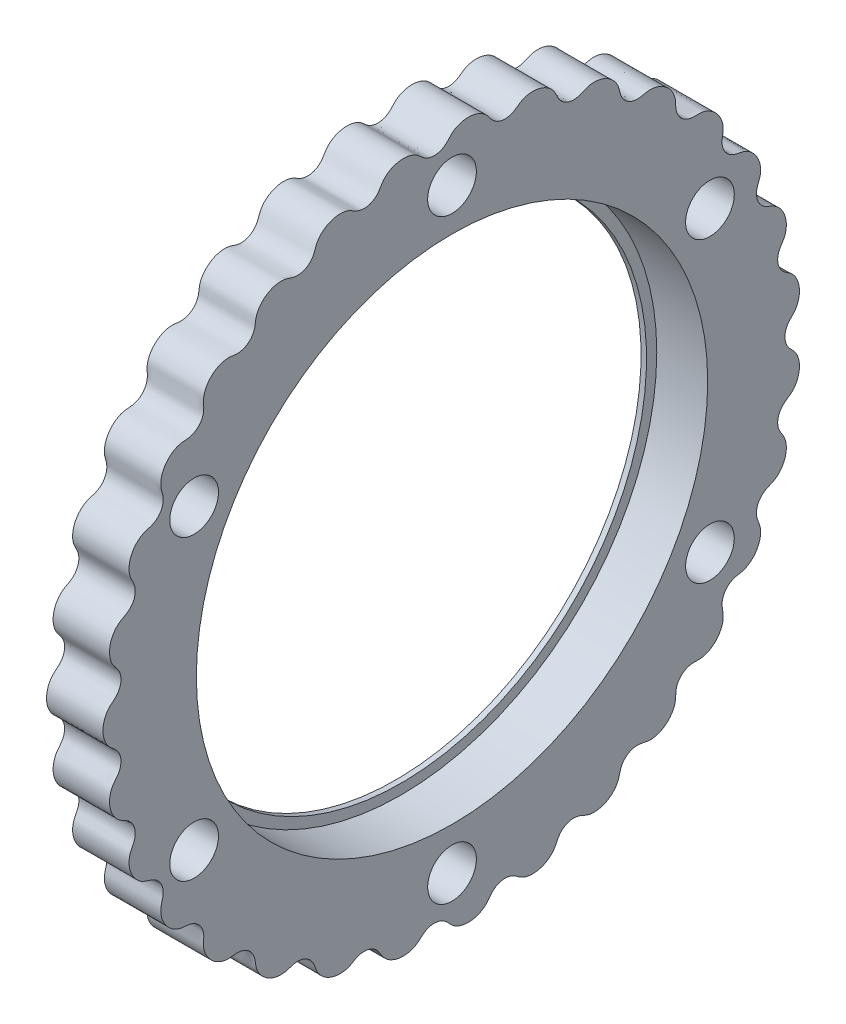
SolidWorks part; units mm, degrees
ref_plane "Front Plane" through (0, 0, 0) normal (0, 0, 1) x (1, 0, 0)
ref_plane "Top Plane" through (0, 0, 0) normal (0, 1, 0) x (1, 0, 0)
ref_plane "Right Plane" through (0, 0, 0) normal (1, 0, 0) x (0, 0, -1)
sketch "Sketch2" plane through (0, 0, 0) normal (0, 0, 1) x (1, 0, 0)
  line L0 (0, 0) -> (58.591, 0) construction
  line L2 (0, 0) -> (18.4, 0)
  line L3 (0, 0) -> (0, 2.5)
  line L4 (0, 2.5) -> (18.4, 2.5)
  line L5 (18.4, 0) -> (18.4, 2.5)
  line L6 (6, 2.5) -> (6, 6)
  line L11 (6, 6) -> (9.97, 6)
  line L16 (12.97, 6) -> (12.97, 3)
  line L17 (12.97, 3) -> (13.6304, 3)
  line L18 (13.6304, 3) -> (13.6304, 2.5)
  line L19 (13.6304, 2.5) -> (6, 2.5)
  line L22 (13.6304, 2.5) -> (16.1104, 2.5)
  line L23 (13.6304, 2.5) -> (13.6304, 4)
  line L24 (13.6304, 4) -> (16.1104, 4)
  line L25 (16.1104, 2.5) -> (16.1104, 4)
  line L27 (6, 6) -> (9.97, 6)
  line L28 (6, 6) -> (6, 9)
  line L29 (6, 9) -> (9.97, 9)
  line L30 (9.97, 6) -> (9.97, 9)
  line L31 (6, 9) -> (6, 8.25)
  line L32 (6, 8.25) -> (5, 8.25)
  line L33 (8.58, 22.001) -> (8.58, 12.476) construction
  line L34 (5, 12.476) -> (12.16, 12.476)
  line L35 (9.97, 9) -> (12.16, 9)
  line L36 (5, 7.5) -> (3, 7.5)
  line L37 (5, 8.25) -> (5, 12.476)
  line L38 (5, 7.5) -> (5, 14)
  line L39 (5, 14) -> (3, 14)
  line L40 (3, 7.5) -> (3, 14)
  line L41 (5, 22.001) -> (12.16, 22.001)
  line L42 (5, 22.001) -> (5, 30.1625)
  line L43 (5, 30.1625) -> (12.16, 30.1625)
  line L44 (12.16, 22.001) -> (12.16, 30.1625)
  line L49 (16.6304, 22.001) -> (16.6304, 7.5)
  line L51 (23.0104, 7.5) -> (23.0104, 6.5)
  line L54 (16.1104, 4) -> (13.6304, 4)
  line L56 (18.0304, 7.5) -> (23.0104, 7.5)
  line L57 (13.16, 22.001) -> (16.6304, 22.001)
  line L58 (16.1104, 3.5) -> (20.0104, 3.5)
  line L59 (29.9004, 14) -> (26.9004, 11)
  line L60 (4, 31.75) -> (18.0304, 31.75)
  line L61 (18.0304, 7.5) -> (23.0104, 7.5)
  line L62 (18.0304, 7.5) -> (18.0304, 12)
  line L63 (18.0304, 12) -> (23.0104, 12)
  line L64 (23.0104, 7.5) -> (23.0104, 12)
  line L65 (18.0304, 31.75) -> (18.0304, 12)
  line L66 (23.0104, 11) -> (26.9004, 11)
  line L67 (34.8004, 23) -> (31.3004, 19.5)
  line L68 (35.8004, 31) -> (38.7904, 33.99)
  line L69 (29.9004, 14) -> (29.9004, 15)
  line L70 (29.9004, 15) -> (22.9304, 15)
  line L71 (22.9304, 15) -> (21.0304, 15)
  line L72 (18.0304, 7.5) -> (16.6304, 7.5)
  line L73 (21.0304, 15) -> (21.0304, 43)
  line L74 (20.0304, 40) -> (10.0704, 40)
  line L75 (10.0704, 40) -> (4, 40)
  line L76 (21.0304, 43) -> (20.0304, 43)
  line L77 (22.9304, 15) -> (29.9004, 15)
  line L78 (22.9304, 15) -> (22.9304, 21)
  line L79 (22.9304, 21) -> (29.9004, 21)
  line L80 (29.9004, 15) -> (29.9004, 21)
  line L81 (10.0704, 40) -> (20.0304, 40)
  line L82 (10.0704, 40) -> (10.0704, 50)
  line L83 (10.0704, 50) -> (20.0304, 50)
  line L84 (20.0304, 40) -> (20.0304, 50)
  line L85 (4, 40) -> (4, 31.75)
  line L86 (12.97, 3) -> (12.97, 2.5)
  line L87 (31.3004, 19.5) -> (29.9004, 19.5)
  line L88 (21.51, 63.5) -> (21.51, 44)
  line L89 (21.51, 63.5) -> (25.9304, 63.5)
  line L90 (25.9304, 63.5) -> (25.9304, 25)
  line L91 (27.8304, 25) -> (25.9304, 25)
  line L92 (10.0704, 48) -> (9, 48)
  line L93 (9, 48) -> (9, 53.476)
  line L94 (9, 53.476) -> (20.0304, 53.476)
  line L95 (20.0304, 53.476) -> (20.0304, 50)
  line L96 (14.5152, 63.001) -> (14.5152, 53.476) construction
  line L97 (9, 63.001) -> (20.0304, 63.001)
  line L98 (9, 63.001) -> (9, 68.2625)
  line L99 (9, 68.2625) -> (20.0304, 68.2625)
  line L100 (20.0304, 63.001) -> (20.0304, 68.2625)
  line L101 (12.97, 6) -> (11.97, 6)
  line L102 (9, 42.5) -> (5, 42.5)
  line L103 (9, 42.5) -> (9, 55)
  line L104 (9, 55) -> (5, 55)
  line L105 (5, 42.5) -> (5, 55)
  line L106 (9.97, 6) -> (10.87, 6)
  line L107 (27.8304, 25) -> (34.8004, 25)
  line L108 (34.8004, 25) -> (34.8004, 23)
  line L109 (0, 0) -> (-2, 0)
  line L110 (0, 0) -> (0, 11)
  line L111 (27.8304, 25) -> (34.8004, 25)
  line L112 (27.8304, 25) -> (27.8304, 32.5)
  line L113 (27.8304, 32.5) -> (34.8004, 32.5)
  line L114 (34.8004, 25) -> (34.8004, 32.5)
  line L115 (35.8004, 31) -> (34.8004, 31)
  line L116 (27.8304, 32.5) -> (27.8304, 64.5)
  line L117 (21.1827, 74.025) -> (6.8477, 74.025)
  line L118 (6.8477, 74.025) -> (6.8477, 76.2)
  line L119 (38.7904, 47.29) -> (30.8304, 55.25)
  line L120 (0, 11) -> (-2, 11)
  line L121 (38.7904, 43.815) -> (30.8529, 43.815)
  line L123 (-4.8, 69.85) -> (1.55, 76.2)
  line L124 (38.7904, 47.29) -> (38.7904, 33.99)
  line L125 (-2, 0) -> (-2, 11)
  line L126 (38.7904, 37.465) -> (30.8529, 37.465)
  line L127 (30.8529, 43.815) -> (30.8529, 37.465)
  line L128 (6, 2.5) -> (6, 0)
  line L129 (0, 63.5) -> (0, 30)
  line L132 (5, 63.5) -> (0, 63.5)
  line L136 (-1.8, 30) -> (-11.76, 30)
  line L138 (-13.76, 25.4) -> (-2, 25.4)
  line L139 (-2, 25.4) -> (-2, 11.5)
  line L140 (27.8304, 64.5) -> (21.1827, 64.5)
  line L141 (-1.8, 30) -> (-11.76, 30)
  line L142 (-1.8, 30) -> (-1.8, 39)
  line L143 (-1.8, 39) -> (-11.76, 39)
  line L144 (-11.76, 30) -> (-11.76, 39)
  line L145 (21.1827, 64.5) -> (21.1827, 74.025)
  line L146 (-12.76, 37) -> (-12.76, 47.29)
  line L147 (-12.76, 37) -> (-11.76, 37)
  line L148 (30.8304, 55.25) -> (30.8304, 76.2)
  line L149 (11.97, 6) -> (11.97, 5.45)
  line L154 (-2, 11.5) -> (1, 11.5)
  line L155 (5, 60.6197) -> (24.05, 60.6197)
  line L160 (5, 60.6197) -> (5, 55.8572)
  line L161 (5, 55.8572) -> (24.05, 55.8572)
  line L166 (24.05, 60.6197) -> (24.05, 55.8572)
  line L167 (5, 60.6197) -> (24.05, 55.8572) construction
  line L172 (5, 55.8572) -> (24.05, 60.6197) construction
  line L173 (24.05, 62.2072) -> (25.9304, 62.2072)
  line L174 (11.97, 5.45) -> (10.87, 5.45)
  line L175 (10.87, 6) -> (10.87, 5.45)
  line L176 (24.05, 62.2072) -> (24.05, 54.2697)
  line L177 (24.05, 54.2697) -> (25.9304, 54.2697)
  line L178 (25.9304, 62.2072) -> (25.9304, 54.2697)
  line L179 (24.05, 62.2072) -> (25.9304, 54.2697) construction
  line L180 (24.05, 54.2697) -> (25.9304, 62.2072) construction
  line L181 (3, 19.6197) -> (15.7, 19.6197)
  line L182 (3, 19.6197) -> (3, 14.8572)
  line L183 (3, 14.8572) -> (15.7, 14.8572)
  line L184 (15.7, 19.6197) -> (15.7, 14.8572)
  line L185 (3, 19.6197) -> (15.7, 14.8572) construction
  line L186 (3, 14.8572) -> (15.7, 19.6197) construction
  line L187 (15.7, 21.2072) -> (16.6304, 21.2072)
  line L188 (15.7, 21.2072) -> (15.7, 13.2697)
  line L189 (15.7, 13.2697) -> (16.6304, 13.2697)
  line L190 (16.6304, 21.2072) -> (16.6304, 13.2697)
  line L191 (15.7, 21.2072) -> (16.6304, 13.2697) construction
  line L192 (15.7, 13.2697) -> (16.6304, 21.2072) construction
  line L193 (1, 11.5) -> (1, 6.5)
  line L194 (1, 6.5) -> (3, 6.5)
  line L195 (23.0104, 6.5) -> (20.0104, 3.5)
  line L196 (5, 63.5) -> (5, 42.5)
  line L197 (5, 42.5) -> (3, 42.5)
  line L198 (3, 42.5) -> (3, 6.5)
  line L199 (6, 0) -> (12.97, 0)
  line L200 (12.97, 0) -> (12.97, 2.5)
  line L201 (18.0304, 31.75) -> (18.0304, 35.875)
  line L202 (18.0304, 35.875) -> (21.0304, 35.875)
  line L203 (30.8304, 76.2) -> (6.8477, 76.2)
  line L204 (3.4027, 69.85) -> (7.8477, 69.85) construction
  line L205 (7.8477, 67.4687) -> (26.8977, 67.4688)
  line L206 (7.8477, 74.025) -> (7.8477, 64.5)
  line L207 (7.8477, 64.5) -> (-1.8, 64.5)
  line L208 (-1.8, 64.5) -> (-1.8, 39)
  line L209 (-12.76, 47.29) -> (-4.8, 55.25)
  line L210 (-4.8, 55.25) -> (-4.8, 69.85)
  line L211 (7.8477, 67.4687) -> (7.8477, 72.2313)
  line L212 (7.8477, 72.2313) -> (26.8977, 72.2313)
  line L213 (26.8977, 67.4688) -> (26.8977, 72.2313)
  line L214 (26.8977, 73.8187) -> (30.8304, 73.8187)
  line L215 (26.8977, 73.8187) -> (26.8977, 65.8813)
  line L216 (26.8977, 65.8813) -> (30.8304, 65.8813)
  line L217 (30.8304, 73.8187) -> (30.8304, 65.8813)
  line L218 (3.4027, 72.2313) -> (25.6277, 72.2313)
  line L219 (3.4027, 72.2313) -> (3.4027, 67.4687)
  line L220 (3.4027, 67.4687) -> (25.6277, 67.4687)
  line L221 (25.6277, 72.2313) -> (25.6277, 67.4687)
  line L222 (25.6277, 69.85) -> (21.1827, 69.85) construction
  line L223 (21.51, 44) -> (22.9304, 44)
  line L224 (22.9304, 44) -> (22.9304, 21)
  line L225 (13.6304, 4) -> (13.6304, 12.2697)
  line L226 (13.6304, 12.2697) -> (13.16, 12.2697)
  line L227 (13.16, 12.2697) -> (13.16, 22.001)
  line L228 (12.16, 9) -> (12.16, 12.476)
  line L229 (-1.8, 30) -> (0, 30)
  line L230 (9, 65.6317) -> (3.4027, 65.6317) construction
  line L231 (20.0304, 65.6317) -> (25.6277, 65.6317) construction
  line L232 (1.55, 76.2) -> (6.8477, 76.2)
  line L233 (-11.76, 30) -> (-13.76, 30)
  line L234 (-13.76, 30) -> (-13.76, 25.4)
  circle A0 centre (26.8804, 25.95) radius 0.95
  circle A1 centre (21.9804, 15.95) radius 0.95
  circle A2 centre (17.3304, 8.2) radius 0.7
  circle A3 centre (10.42, 6.45) radius 0.45
  circle A4 centre (-0.9, 30.9) radius 0.9
  point P7 (24.9902, 58.2385)
  point P131 (16.1652, 17.2385)
  point P135 (14.525, 58.2385)
  point P146 (9.35, 17.2385)
sketch "Sketch3" plane through (0, 0, 0) normal (1, 0, 0) x (0, 0, -1)
  line L0 (0, 0) -> (0, 69.85) construction
  line L1 (0, 0) -> (13.6271, 68.5079) construction
  line L2 (0, 0) -> (0, 58.2385) construction
  line L3 (0, 0) -> (50.436, 29.1192) construction
  line L4 (0, 0) -> (0, 31.75) construction
  line L5 (0, 0) -> (12.1502, 29.3332) construction
  line L6 (0, 0) -> (0, 17.2385) construction
  line L7 (0, 0) -> (14.929, 8.6192) construction
  line L8 (0, 0) -> (0, 58.2385) construction
  line L9 (0, 0) -> (50.436, 29.1192) construction
  line L10 (0, 0) -> (5.9583, 29.9542) construction
  line L11 (0, 0) -> (16.9677, 25.394) construction
  circle A0 centre (0, 0) radius 69.85 construction
  circle A1 centre (0, 0) radius 58.2385 construction
  circle A2 centre (0, 0) radius 31.75 construction
  circle A3 centre (0, 0) radius 17.2385 construction
  circle A4 centre (0, 69.85) radius 3.175
  circle A5 centre (0, 58.2385) radius 4.7625
  circle A6 centre (0, 31.75) radius 3.175
  circle A7 centre (0, 17.2385) radius 4.7625
  circle A8 centre (13.6271, 68.5079) radius 3.175
  circle A9 centre (26.7304, 64.533) radius 3.175
  circle A10 centre (38.8066, 58.0782) radius 3.175
  circle A11 centre (49.3914, 49.3914) radius 3.175
  circle A12 centre (58.0782, 38.8066) radius 3.175
  circle A13 centre (64.533, 26.7304) radius 3.175
  circle A14 centre (68.5079, 13.6271) radius 3.175
  circle A15 centre (69.85, 0) radius 3.175
  circle A16 centre (68.5079, -13.6271) radius 3.175
  circle A17 centre (64.533, -26.7304) radius 3.175
  circle A18 centre (58.0782, -38.8066) radius 3.175
  circle A19 centre (49.3914, -49.3914) radius 3.175
  circle A20 centre (38.8066, -58.0782) radius 3.175
  circle A21 centre (26.7304, -64.533) radius 3.175
  circle A22 centre (13.6271, -68.5079) radius 3.175
  circle A23 centre (0, -69.85) radius 3.175
  circle A24 centre (-13.6271, -68.5079) radius 3.175
  circle A25 centre (-26.7304, -64.533) radius 3.175
  circle A26 centre (-38.8066, -58.0782) radius 3.175
  circle A27 centre (-49.3914, -49.3914) radius 3.175
  circle A28 centre (-58.0782, -38.8066) radius 3.175
  circle A29 centre (-64.533, -26.7304) radius 3.175
  circle A30 centre (-68.5079, -13.6271) radius 3.175
  circle A31 centre (-69.85, 0) radius 3.175
  circle A32 centre (-68.5079, 13.6271) radius 3.175
  circle A33 centre (-64.533, 26.7304) radius 3.175
  circle A34 centre (-58.0782, 38.8066) radius 3.175
  circle A35 centre (-49.3914, 49.3914) radius 3.175
  circle A36 centre (-38.8066, 58.0782) radius 3.175
  circle A37 centre (-26.7304, 64.533) radius 3.175
  circle A38 centre (-13.6271, 68.5079) radius 3.175
  circle A47 centre (50.436, 29.1192) radius 4.7625
  circle A48 centre (50.436, -29.1192) radius 4.7625
  circle A49 centre (0, -58.2385) radius 4.7625
  circle A50 centre (-50.436, -29.1192) radius 4.7625
  circle A51 centre (-50.436, 29.1192) radius 4.7625
  circle A58 centre (12.1502, 29.3332) radius 3.175
  circle A59 centre (22.4506, 22.4506) radius 3.175
  circle A60 centre (29.3332, 12.1502) radius 3.175
  circle A61 centre (31.75, 0) radius 3.175
  circle A62 centre (29.3332, -12.1502) radius 3.175
  circle A63 centre (22.4506, -22.4506) radius 3.175
  circle A64 centre (12.1502, -29.3332) radius 3.175
  circle A65 centre (0, -31.75) radius 3.175
  circle A66 centre (-12.1502, -29.3332) radius 3.175
  circle A67 centre (-22.4506, -22.4506) radius 3.175
  circle A68 centre (-29.3332, -12.1502) radius 3.175
  circle A69 centre (-31.75, 0) radius 3.175
  circle A70 centre (-29.3332, 12.1502) radius 3.175
  circle A71 centre (-22.4506, 22.4506) radius 3.175
  circle A72 centre (14.929, 8.6192) radius 4.7625
  circle A73 centre (14.929, -8.6192) radius 4.7625
  circle A74 centre (0, -17.2385) radius 4.7625
  circle A75 centre (-14.929, -8.6192) radius 4.7625
  circle A76 centre (-14.929, 8.6192) radius 4.7625
  circle A77 centre (0, 0) radius 50
  circle A78 centre (0, 0) radius 9
  circle A79 centre (-12.1502, 29.3332) radius 3.175
  circle A80 centre (0, 0) radius 76.2
  circle A81 centre (0, 0) radius 74.025
  circle A82 centre (0, 69.85) radius 3.9687
  circle A83 centre (49.3914, 49.3914) radius 3.9687
  circle A84 centre (69.85, 0) radius 3.9688
  circle A85 centre (49.3914, -49.3914) radius 3.9687
  circle A86 centre (0, -69.85) radius 3.9687
  circle A87 centre (-49.3914, -49.3914) radius 3.9687
  circle A88 centre (-69.85, 0) radius 3.9688
  circle A89 centre (-49.3914, 49.3914) radius 3.9687
  circle A90 centre (0, 69.85) radius 2.3812
  circle A91 centre (13.6271, 68.5079) radius 2.3812
  circle A92 centre (26.7304, 64.533) radius 2.3813
  circle A93 centre (38.8066, 58.0782) radius 2.3812
  circle A94 centre (49.3914, 49.3914) radius 2.3812
  circle A95 centre (58.0782, 38.8066) radius 2.3812
  circle A96 centre (64.533, 26.7304) radius 2.3813
  circle A97 centre (68.5079, 13.6271) radius 2.3813
  circle A98 centre (69.85, 0) radius 2.3813
  circle A99 centre (68.5079, -13.6271) radius 2.3813
  circle A100 centre (64.533, -26.7304) radius 2.3813
  circle A101 centre (58.0782, -38.8066) radius 2.3812
  circle A102 centre (49.3914, -49.3914) radius 2.3812
  circle A103 centre (38.8066, -58.0782) radius 2.3812
  circle A104 centre (26.7304, -64.533) radius 2.3813
  circle A105 centre (13.6271, -68.5079) radius 2.3812
  circle A106 centre (0, -69.85) radius 2.3812
  circle A107 centre (-13.6271, -68.5079) radius 2.3812
  circle A108 centre (-26.7304, -64.533) radius 2.3813
  circle A109 centre (-38.8066, -58.0782) radius 2.3812
  circle A110 centre (-49.3914, -49.3914) radius 2.3812
  circle A111 centre (-58.0782, -38.8066) radius 2.3812
  circle A112 centre (-64.533, -26.7304) radius 2.3812
  arc A113 (3.0399, 30.8338) -> (8.9911, 29.65) centre (5.9583, 29.9542) cw
  arc A114 (14.6081, 27.3234) -> (19.6532, 23.9523) centre (16.9677, 25.394) cw
  arc A115 (23.9523, 19.6532) -> (27.3234, 14.6081) centre (25.394, 16.9677) cw
  arc A116 (29.65, 8.9911) -> (30.8338, 3.0399) centre (29.9542, 5.9583) cw
  arc A117 (30.8338, -3.0399) -> (29.65, -8.9911) centre (29.9542, -5.9583) cw
  arc A118 (27.3234, -14.6081) -> (23.9523, -19.6532) centre (25.394, -16.9677) cw
  arc A119 (19.6532, -23.9523) -> (14.6081, -27.3234) centre (16.9677, -25.394) cw
  arc A120 (8.9911, -29.65) -> (3.0399, -30.8338) centre (5.9583, -29.9542) cw
  arc A121 (-3.0399, -30.8338) -> (-8.9911, -29.65) centre (-5.9583, -29.9542) cw
  arc A122 (-14.6081, -27.3234) -> (-19.6532, -23.9523) centre (-16.9677, -25.394) cw
  arc A123 (-23.9523, -19.6532) -> (-27.3234, -14.6081) centre (-25.394, -16.9677) cw
  arc A124 (-29.65, -8.9911) -> (-30.8338, -3.0399) centre (-29.9542, -5.9583) cw
  arc A125 (-30.8338, 3.0399) -> (-29.65, 8.9911) centre (-29.9542, 5.9583) cw
  arc A126 (-27.3234, 14.6081) -> (-23.9523, 19.6532) centre (-25.394, 16.9677) cw
  arc A127 (-19.6532, 23.9523) -> (-14.6081, 27.3234) centre (-16.9677, 25.394) cw
  arc A128 (-8.9911, 29.65) -> (-3.0399, 30.8338) centre (-5.9583, 29.9542) cw
  arc A129 (26.9875, 0) -> (26.9932, 0.1932) centre (30.2705, 0) cw
  arc A130 (65.0988, 0.2771) -> (65.0875, 0) centre (68.4964, 0) ccw
  circle A131 centre (1.5875, 0) radius 40
  circle A132 centre (1.5875, 0) radius 2.5
  circle A133 centre (1.5875, 0) radius 3
  circle A134 centre (1.5875, 0) radius 43
  circle A135 centre (-68.5079, -13.6271) radius 2.3813
  circle A136 centre (-69.85, 0) radius 2.3813
  circle A137 centre (-68.5079, 13.6271) radius 2.3813
  circle A138 centre (-64.533, 26.7304) radius 2.3812
  circle A139 centre (-58.0782, 38.8066) radius 2.3812
  circle A140 centre (-49.3914, 49.3914) radius 2.3812
  circle A141 centre (-38.8066, 58.0782) radius 2.3812
  circle A142 centre (-26.7304, 64.533) radius 2.3813
  circle A143 centre (-13.6271, 68.5079) radius 2.3812
  circle A144 centre (0, 58.2385) radius 2.3812
  circle A145 centre (0, 58.2385) radius 3.9688
  circle A146 centre (50.436, 29.1192) radius 3.9688
  circle A147 centre (50.436, 29.1192) radius 2.3813
  circle A148 centre (50.436, -29.1192) radius 3.9687
  circle A149 centre (50.436, -29.1192) radius 2.3812
  circle A150 centre (0, -58.2385) radius 3.9687
  circle A151 centre (0, -58.2385) radius 2.3812
  circle A152 centre (-50.436, -29.1192) radius 3.9687
  circle A153 centre (-50.436, -29.1192) radius 2.3812
  circle A154 centre (-50.436, 29.1192) radius 3.9687
  circle A155 centre (-50.436, 29.1192) radius 2.3812
  spline S1 degree 4 number of poles 499 (26.9875, 0) -> (26.9932, 0.1932)
  spline S3 degree 4 number of poles 617 (65.0875, 0) -> (65.0988, 0.2771)
  point P116 (0, 0)
  point P225 (0, 0)
sketch "Sketch6" plane through (0, 0, 0) normal (0, 0, 1) x (1, 0, 0)
  line L0 (20.0304, 53.476) -> (20.0304, 50) construction
  line L1 (10.0704, 50) -> (20.0304, 50) construction
  line L2 (10.0704, 40) -> (10.0704, 50) construction
  line L3 (10.0704, 48) -> (9, 48) construction
  line L4 (9, 48) -> (9, 53.476) construction
  line L5 (9, 53.476) -> (20.0304, 53.476) construction
  line L6 (20.0304, 53.476) -> (20.0304, 50)
  line L7 (10.0704, 50) -> (20.0304, 50)
  line L8 (10.0704, 48) -> (10.0704, 50)
  line L9 (10.0704, 48) -> (9, 48)
  line L10 (9, 48) -> (9, 53.476)
  line L11 (9, 53.476) -> (20.0304, 53.476)
revolve "Revolve2" add sketch "Sketch6" angle 360 about L0
sketch "Sketch7" plane through (0, 0, 0) normal (1, 0, 0) x (0, 0, -1)
  circle A0 centre (0, 0) radius 50 construction
  circle A1 centre (-50.436, -29.1192) radius 4.7625 construction
  circle A2 centre (0, -58.2385) radius 4.7625 construction
  circle A3 centre (50.436, -29.1192) radius 4.7625 construction
  circle A4 centre (50.436, 29.1192) radius 4.7625 construction
  circle A5 centre (0, 58.2385) radius 4.7625 construction
  circle A6 centre (-50.436, 29.1192) radius 4.7625 construction
  circle A7 centre (0, 0) radius 50
  circle A8 centre (-50.436, -29.1192) radius 4.7625
  circle A9 centre (0, -58.2385) radius 4.7625
  circle A10 centre (50.436, -29.1192) radius 4.7625
  circle A11 centre (50.436, 29.1192) radius 4.7625
  circle A12 centre (0, 58.2385) radius 4.7625
  circle A13 centre (-50.436, 29.1192) radius 4.7625
  arc A14 (65.0988, 0.2771) -> (65.0875, 0) centre (68.4964, 0) ccw construction
  arc A15 (65.0988, 0.2771) -> (65.0875, 0) centre (68.4964, 0) ccw
  spline S0 degree 4 number of poles 617 (65.0875, 0) -> (65.0988, 0.2771) construction
  spline S1 degree 4 number of poles 617 (65.0875, 0) -> (65.0988, 0.2771)
extrude "Boss-Extrude1" add sketch "Sketch7" along normal up to vertex (20.0304 mm away) from vertex up to point (20.0304, 68.2625, 0) starting at point (9, 68.2625, 0)
